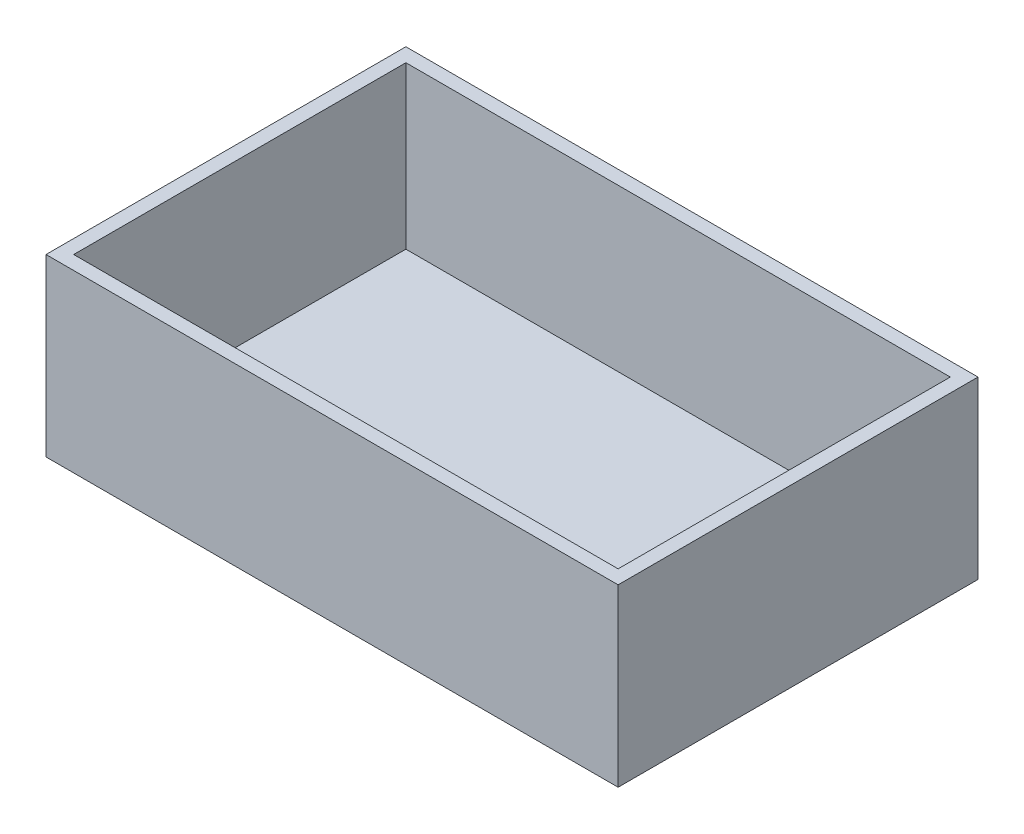
SolidWorks part; units mm, degrees
ref_plane "Front Plane" through (0, 0, 0) normal (0, 0, 1) x (1, 0, 0)
ref_plane "Top Plane" through (0, 0, 0) normal (0, 1, 0) x (1, 0, 0)
ref_plane "Right Plane" through (0, 0, 0) normal (1, 0, 0) x (0, 0, -1)
sketch "Sketch1" plane through (0, 0, 0) normal (0, 1, 0) x (1, 0, 0)
  line L1 (0, 0) -> (787.4, 0)
  line L2 (0, 0) -> (0, 495.3)
  line L3 (0, 495.3) -> (787.4, 495.3)
  line L4 (787.4, 0) -> (787.4, 495.3)
  dimension "D1" = 787.4
  dimension "D2" = 495.3
extrude "Boss-Extrude1" add sketch "Sketch1" along normal blind 241.3
shell "Shell1" thickness 19.05 removed face at (393.7, 241.3, -247.65)
